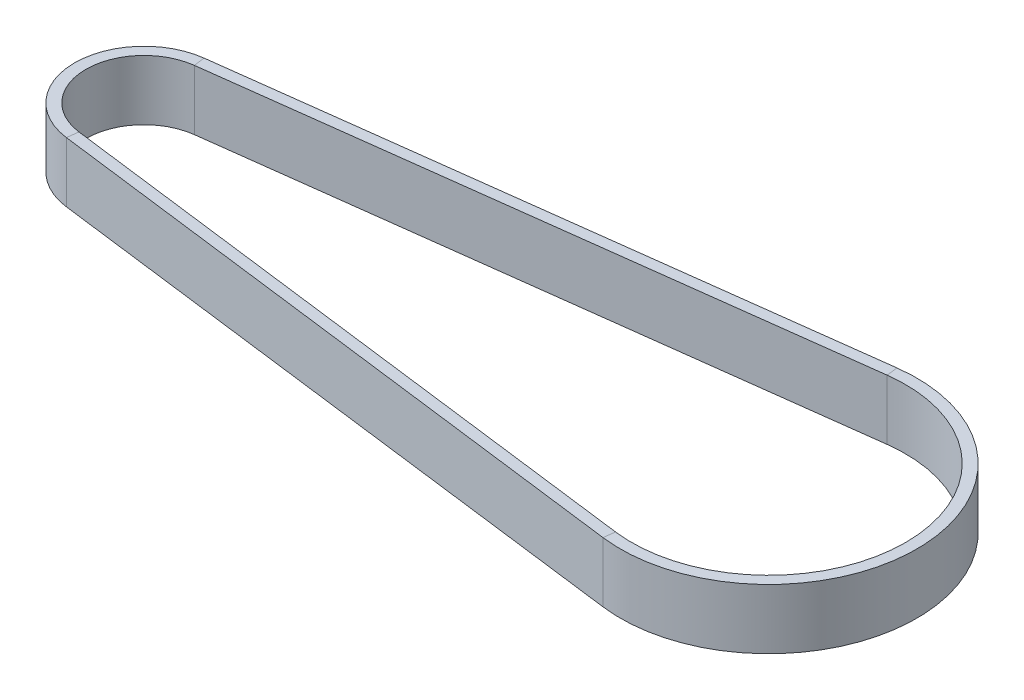
SolidWorks part; units mm, degrees
ref_plane "Front Plane" through (0, 0, 0) normal (0, 0, 1) x (1, 0, 0)
ref_plane "Top Plane" through (0, 0, 0) normal (0, 1, 0) x (1, 0, 0)
ref_plane "Right Plane" through (0, 0, 0) normal (1, 0, 0) x (0, 0, -1)
ref_axis "X" through (-88.99, 0, 0) along (1, 0, 0)
ref_axis "Y" through (0, 0, -88.99) along (0, 0, 1)
ref_axis "Z" through (0, 55, 0) along (0, -1, 0)
sketch "Sketch1" plane through (0, 0, 0) normal (0, 1, 0) x (1, 0, 0)
  line L0 (911.2465, -166.4268) -> (747.3401, -145.5944)
  line L1 (747.3401, -111.8657) -> (911.2465, -91.0333)
  arc A0 (911.2465, -166.4268) -> (911.2465, -91.0333) centre (916.0377, -128.7301) ccw
  arc A1 (747.3401, -111.8657) -> (747.3401, -145.5944) centre (749.4835, -128.7301) ccw
  point P2 (916.0377, -128.7301)
  point P4 (0, 0)
  point P7 (749.4835, -128.7301)
  point P8 (0, 0)
  point P10 (749.4835, -128.7301)
  point P11 (0, 0)
  dimension "D1" = 38
  dimension "D2" = 17
  dimension "D3" = 166.5542
ref_plane "Plane1" through (911.2465, 0, 91.0333) normal (0.992, 0, -0.1261) x (-0.1261, 0, -0.992)
sketch "Sketch2" plane through (911.2465, 0, 91.0333) normal (0.992, 0, -0.1261) x (-0.1261, 0, -0.992)
  line L0 (0, 0) -> (-33.4595, 0) construction
  line L1 (-1.5, 8) -> (1.5, 8)
  line L2 (-1.5, 8) -> (-1.5, -8)
  line L3 (-1.5, -8) -> (1.5, -8)
  line L4 (1.5, 8) -> (1.5, -8)
  line L5 (-1.5, 8) -> (1.5, -8) construction
  line L6 (-1.5, -8) -> (1.5, 8) construction
  point P0 (0, 0)
  dimension "D1" = 3
  dimension "D2" = 16
sweep "Sweep1" add profiles "Sketch2" path "Sketch1"
